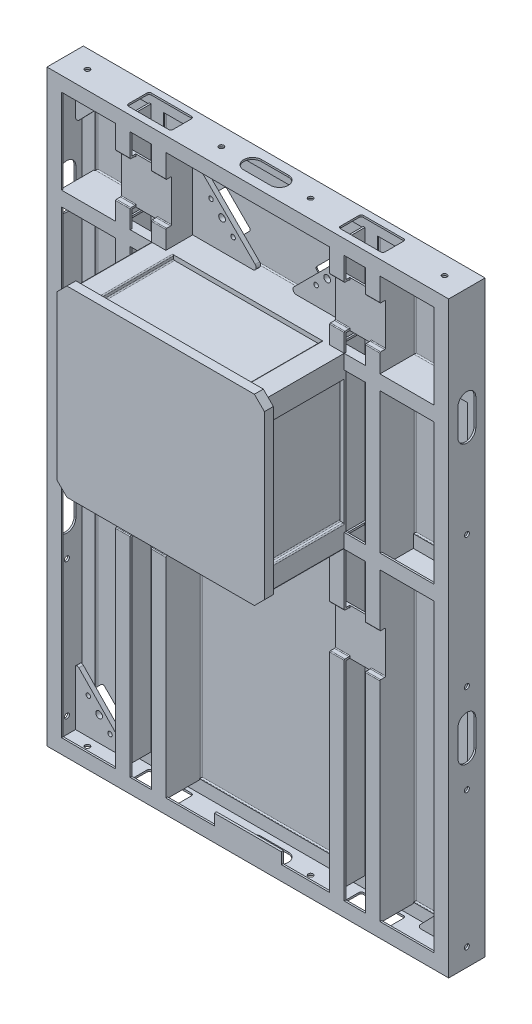
SolidWorks part; units mm, degrees
ref_plane "Alzado" through (0, 0, 0) normal (0, 0, 1) x (1, 0, 0)
ref_plane "Planta" through (0, 0, 0) normal (0, 1, 0) x (1, 0, 0)
ref_plane "Vista lateral" through (0, 0, 0) normal (1, 0, 0) x (0, 0, -1)
sketch "Croquis1" plane through (0, 0, 0) normal (0, 0, 1) x (1, 0, 0)
  line L1 (0, 0) -> (900, 0)
  line L2 (0, 0) -> (0, 2635)
  line L3 (0, 2635) -> (900, 2635)
  line L4 (900, 0) -> (900, 2635)
  dimension "D1" = 2635
  dimension "D2" = 900
extrude "Saliente-Extruir1" add sketch "Croquis1" along normal blind 5
sketch "Croquis3" plane through (0, 0, 5) normal (0, 0, 1) x (1, 0, 0)
  line L0 (900, 2635) -> (0, 2635) construction
  line L1 (0, 0) -> (65, 0)
  line L2 (0, 0) -> (0, 2125)
  line L3 (0, 2635) -> (65, 2635)
  line L4 (65, 65) -> (65, 1430)
  line L5 (900, 0) -> (900, 2635) construction
  line L6 (0, 2635) -> (900, 2635)
  line L7 (0, 2635) -> (0, 2570)
  line L8 (65, 2570) -> (308, 2570)
  line L9 (900, 2635) -> (900, 2570)
  line L10 (373, 2190) -> (468, 2190)
  line L11 (0, 0) -> (900, 0)
  line L12 (0, 0) -> (0, 65)
  line L13 (65, 65) -> (308, 65)
  line L14 (900, 0) -> (900, 65)
  line L15 (308, 0) -> (373, 0)
  line L16 (308, 65) -> (308, 1430)
  line L17 (308, 2635) -> (373, 2635)
  line L18 (373, 65) -> (373, 1430)
  line L19 (468, 0) -> (533, 0)
  line L20 (468, 65) -> (468, 1430)
  line L21 (468, 2635) -> (533, 2635)
  line L22 (533, 65) -> (533, 1430)
  line L23 (65, 1430) -> (308, 1430)
  line L24 (0, 1430) -> (0, 1495)
  line L25 (65, 1495) -> (308, 1495)
  line L26 (900, 1430) -> (900, 1495)
  line L27 (65, 2125) -> (308, 2125)
  line L28 (0, 2125) -> (0, 2190)
  line L29 (65, 2190) -> (308, 2190)
  line L30 (900, 2125) -> (900, 2190)
  line L31 (308, 2190) -> (308, 2570)
  line L32 (373, 2190) -> (373, 2570)
  line L33 (373, 2125) -> (468, 2125)
  line L34 (468, 2190) -> (468, 2570)
  line L35 (533, 2190) -> (900, 2190)
  line L36 (533, 2190) -> (533, 2570)
  line L37 (533, 2125) -> (900, 2125)
  line L38 (533, 2570) -> (900, 2570)
  line L39 (373, 2570) -> (468, 2570)
  line L40 (65, 2190) -> (65, 2570)
  line L41 (373, 1495) -> (468, 1495)
  line L42 (308, 1495) -> (308, 2125)
  line L43 (373, 1495) -> (373, 2125)
  line L44 (373, 1430) -> (468, 1430)
  line L45 (533, 1430) -> (900, 1430)
  line L46 (533, 1495) -> (900, 1495)
  line L47 (533, 1495) -> (533, 2125)
  line L48 (468, 1495) -> (468, 2125)
  line L49 (65, 1495) -> (65, 2125)
  line L50 (373, 65) -> (468, 65)
  line L51 (533, 65) -> (900, 65)
  line L52 (0, 2190) -> (0, 2635)
  line M11 (0, 2635) -> (0, 0)
  line M12 (0, 0) -> (900, 0)
  line M13 (900, 0) -> (900, 2635)
  line M14 (900, 2635) -> (0, 2635)
  dimension "D1" = 65
  dimension "D2" = 65
  dimension "D3" = 65
  dimension "D4" = 65
  dimension "D5" = 65
  dimension "D6" = 95
  dimension "D7" = 65
  dimension "D8" = 65
  dimension "D9" = 243
  dimension "D10" = 630
  dimension "D11" = 380
extrude "Saliente-Extruir2" add sketch "Croquis3" along normal blind 8 contours L51 L22 L45 L46 L47 L37 L35 L36 L38 L6 L2 L11 L50 L18 L44 L20 L48 L41 L43 L33 L4 L23 L16 L13 L32 L39 L34 M13 M14 M11 M12
sketch "Croquis4" plane through (0, 0, 13) normal (0, 0, 1) x (1, 0, 0)
  line L0 (308, 2627) -> (308, 2190)
  line L1 (533, 8) -> (533, 1430)
  line L2 (8, 2190) -> (308, 2190)
  line L3 (8, 2182) -> (308, 2182)
  line L4 (8, 1430) -> (308, 1430)
  line L5 (8, 1438) -> (308, 1438)
  line L6 (316, 2627) -> (316, 2190)
  line L7 (525, 8) -> (525, 1430)
  line L8 (8, 2182) -> (8, 1438)
  line L9 (316, 2190) -> (525, 2190)
  line L10 (316, 2182) -> (525, 2182)
  line L11 (8, 2190) -> (900, 2190) construction
  line L12 (308, 2182) -> (308, 1438)
  line L13 (8, 2182) -> (900, 2182) construction
  line L14 (316, 2182) -> (316, 1438)
  line L15 (308, 2627) -> (308, 8) construction
  line L16 (533, 2190) -> (900, 2190)
  line L17 (316, 2627) -> (316, 8) construction
  line L18 (525, 2190) -> (525, 2627)
  line L19 (533, 2190) -> (533, 2627)
  line L20 (525, 8) -> (525, 2627) construction
  line L21 (533, 2182) -> (900, 2182)
  line L22 (533, 8) -> (533, 2627) construction
  line L23 (308, 2627) -> (8, 2627)
  line L24 (525, 2627) -> (316, 2627)
  line L25 (316, 1438) -> (525, 1438)
  line L26 (900, 2627) -> (8, 2627)
  line L27 (8, 8) -> (900, 8)
  line L28 (8, 2627) -> (8, 8)
  line L29 (900, 2627) -> (533, 2627)
  line L30 (8, 8) -> (308, 8)
  line L31 (8, 2627) -> (8, 2190)
  line L32 (308, 1430) -> (308, 8)
  line L33 (8, 1438) -> (900, 1438) construction
  line L34 (316, 1430) -> (525, 1430)
  line L35 (316, 1430) -> (316, 8)
  line L36 (8, 1430) -> (900, 1430) construction
  line L37 (533, 1438) -> (900, 1438)
  line L38 (525, 1438) -> (525, 2182)
  line L39 (533, 1430) -> (900, 1430)
  line L40 (533, 1438) -> (533, 2182)
  line L41 (8, 1430) -> (8, 8)
  line L42 (316, 8) -> (525, 8)
  line L43 (533, 8) -> (900, 8)
  line L44 (8, 1430) -> (8, 1438)
  line L59 (8, 1430) -> (65, 1430)
  line L60 (8, 1430) -> (8, 1438)
  line L61 (8, 1438) -> (65, 1438)
  line L62 (65, 1430) -> (65, 1438)
  line L71 (900, 2635) -> (0, 2635)
  line L72 (900, 2635) -> (900, 0)
  line L73 (900, 0) -> (0, 0)
  line L74 (0, 2635) -> (0, 0)
  line M33 (533, 65) -> (533, 1430)
  line M34 (533, 1430) -> (900, 1430)
  line M35 (900, 1430) -> (900, 1495)
  line M37 (533, 1495) -> (533, 2125)
  line M39 (900, 2125) -> (900, 2190)
  line M40 (900, 2190) -> (533, 2190)
  line M41 (533, 2190) -> (533, 2570)
  line M43 (900, 2570) -> (900, 2635)
  line M44 (900, 2635) -> (0, 2635)
  line M45 (0, 2635) -> (0, 0)
  line M46 (0, 0) -> (900, 0)
  line M47 (900, 0) -> (900, 65)
  line M50 (373, 1430) -> (468, 1430)
  line M57 (65, 1430) -> (308, 1430)
  line M58 (308, 1430) -> (308, 65)
  line M63 (468, 2190) -> (373, 2190)
  line M64 (308, 2190) -> (65, 2190)
  line M67 (308, 2570) -> (308, 2190)
  dimension "D1" = 8
  dimension "D2" = 8
  dimension "D3" = 8
  dimension "D4" = 8
  dimension "D5" = 8
extrude "Saliente-Extruir4" add sketch "Croquis4" along normal blind 150 separate body contours L43 L1 L37 L40 L21 L19 L29 L42 L35 L34 L7 L41 L4 L32 L30 L38 L25 L14 L10 L31 L23 L0 L2 L24 L18 L9 M33 M34 M35 M37 M39 M40 M41 M43 M44 M45 M46 M47 M50 M57 M58 M67 M64 M63
sketch "Croquis6" plane through (0, 0, 163) normal (0, 0, 1) x (1, 0, 0)
  line L1 (65, 2570) -> (308, 2570)
  line L2 (65, 2570) -> (65, 2190)
  line L3 (65, 2190) -> (308, 2190)
  line L4 (308, 2570) -> (308, 2190)
  line L5 (373, 2570) -> (468, 2570)
  line L6 (373, 2570) -> (373, 2190)
  line L7 (373, 2190) -> (468, 2190)
  line L8 (468, 2570) -> (468, 2190)
  line L9 (65, 2125) -> (308, 2125)
  line L10 (65, 2125) -> (65, 1495)
  line L11 (65, 1495) -> (308, 1495)
  line L12 (308, 2125) -> (308, 1495)
  line L13 (373, 1495) -> (468, 1495)
  line L14 (373, 1495) -> (373, 2125)
  line L15 (373, 2125) -> (468, 2125)
  line L16 (900, 65) -> (533, 65)
  line L17 (533, 65) -> (533, 1430)
  line L18 (533, 1430) -> (900, 1430)
  line L31 (900, 0) -> (900, 65)
  line L32 (900, 65) -> (533, 65)
  line L33 (533, 65) -> (533, 1430)
  line L47 (900, 0) -> (900, 65)
  line L48 (468, 1495) -> (468, 2125)
  line L49 (65, 1430) -> (308, 1430)
  line L50 (65, 1430) -> (65, 65)
  line L51 (65, 65) -> (308, 65)
  line L52 (308, 1430) -> (308, 65)
  line L53 (373, 65) -> (468, 65)
  line L54 (373, 65) -> (373, 1430)
  line L55 (373, 1430) -> (468, 1430)
  line L56 (468, 65) -> (468, 1430)
  line L64 (533, 1430) -> (900, 1430)
  line L66 (900, 1430) -> (900, 1495)
  line L68 (900, 1430) -> (900, 1495)
  line L70 (900, 1495) -> (533, 1495)
  line L72 (900, 1495) -> (533, 1495)
  line L74 (533, 1495) -> (533, 2125)
  line L76 (533, 1495) -> (533, 2125)
  line L78 (533, 2125) -> (900, 2125)
  line L80 (533, 2125) -> (900, 2125)
  line L82 (900, 2125) -> (900, 2190)
  line L84 (900, 2125) -> (900, 2190)
  line L86 (900, 2190) -> (533, 2190)
  line L87 (900, 2190) -> (533, 2190)
  line L88 (533, 2190) -> (533, 2570)
  line L89 (533, 2190) -> (533, 2570)
  line L90 (533, 2570) -> (900, 2570)
  line L91 (533, 2570) -> (900, 2570)
  line L92 (900, 2570) -> (900, 2635)
  line L93 (900, 2570) -> (900, 2635)
  line L94 (900, 2635) -> (0, 2635)
  line L95 (900, 2635) -> (0, 2635)
  line L96 (0, 2635) -> (0, 0)
  line L97 (0, 2635) -> (0, 0)
  line L98 (0, 0) -> (900, 0)
  line L99 (0, 0) -> (900, 0)
  dimension "D1" = 0
extrude "Saliente-Extruir5" add sketch "Croquis6" against normal blind 8
sketch "Croquis7" plane through (0, 0, 0) normal (-1, 0, 0) x (0, 0, 1)
  line L0 (0, 2135) -> (163, 2135) construction
  line L1 (0, 2635) -> (0, 0) construction
  line L2 (163, 2635) -> (163, 0) construction
  line L3 (81.5, 2635) -> (81.5, 0) construction
  line L4 (163, 2635) -> (13, 2635) construction
  line L5 (163, 0) -> (13, 0) construction
  line L6 (81.5, 2195) -> (81.5, 2075) construction
  line L7 (121.5, 2195) -> (121.5, 2075)
  line L8 (41.5, 2195) -> (41.5, 2075)
  line L9 (81.5, 950) -> (81.5, 830) construction
  line L10 (121.5, 950) -> (121.5, 830)
  line L11 (41.5, 950) -> (41.5, 830)
  arc A0 (121.5, 2195) -> (41.5, 2195) centre (81.5, 2195) ccw
  arc A1 (41.5, 2075) -> (121.5, 2075) centre (81.5, 2075) ccw
  circle A2 centre (81.5, 1680) radius 11
  circle A3 centre (81.5, 1090) radius 11
  circle A4 centre (81.5, 80) radius 11
  circle A5 centre (81.5, 690) radius 11
  arc A6 (121.5, 950) -> (41.5, 950) centre (81.5, 950) ccw
  arc A7 (41.5, 830) -> (121.5, 830) centre (81.5, 830) ccw
  point P6 (81.5, 2135)
  point P15 (81.5, 2135)
  point P30 (81.5, 890)
  dimension "D3" = 40
  dimension "D4" = 22
  dimension "D8" = 200
  dimension "D1" = 500
  dimension "D2" = 60
  dimension "D5" = 955
  dimension "D6" = 80
  dimension "D7" = 890
  dimension "D9" = 200
extrude "Cortar-Extruir1" cut sketch "Croquis7" against normal blind 50
sketch "Croquis9" plane through (0, 0, 13) normal (0, 0, 1) x (1, 0, 0)
  line L0 (533, 8) -> (900, 8) construction
  line L1 (533, 8) -> (533, 1430) construction
  line L2 (533, 1430) -> (900, 1430) construction
  line L3 (533, 1438) -> (900, 1438) construction
  line L4 (533, 1438) -> (533, 2182) construction
  line L5 (533, 2182) -> (900, 2182) construction
  line L6 (533, 2190) -> (900, 2190) construction
  line L7 (533, 2190) -> (533, 2627) construction
  line L8 (900, 2627) -> (533, 2627) construction
  line L9 (8, 1430) -> (8, 1438) construction
  line L10 (8, 1430) -> (8, 1438) construction
  line L11 (65, 2570) -> (900, 2570)
  line L12 (316, 65) -> (525, 65)
  line L13 (65, 65) -> (900, 65)
  line L14 (8, 2182) -> (8, 1438) construction
  line L15 (8, 2182) -> (308, 2182) construction
  line L16 (308, 2182) -> (308, 1438) construction
  line L17 (8, 1438) -> (308, 1438) construction
  line L18 (8, 1430) -> (308, 1430) construction
  line L19 (308, 1430) -> (308, 8) construction
  line L20 (8, 8) -> (308, 8) construction
  line L21 (8, 1430) -> (8, 8) construction
  line L22 (316, 2627) -> (316, 2190) construction
  line L23 (316, 2190) -> (525, 2190) construction
  line L24 (525, 2190) -> (525, 2627) construction
  line L25 (525, 2627) -> (316, 2627) construction
  line L26 (308, 2627) -> (308, 2190) construction
  line L27 (308, 2627) -> (8, 2627) construction
  line L28 (8, 2627) -> (8, 2190) construction
  line L29 (8, 2190) -> (308, 2190) construction
  line L30 (525, 1438) -> (525, 2182) construction
  line L31 (316, 2182) -> (525, 2182) construction
  line L32 (316, 2182) -> (316, 1438) construction
  line L33 (316, 1438) -> (525, 1438) construction
  line L34 (525, 8) -> (525, 1430) construction
  line L35 (316, 8) -> (525, 8) construction
  line L36 (316, 1430) -> (316, 8) construction
  line L37 (316, 1430) -> (525, 1430) construction
  line L38 (900, 2635) -> (0, 2635) construction
  line L39 (0, 2635) -> (0, 0) construction
  line L40 (900, 0) -> (0, 0) construction
  line L41 (900, 2635) -> (900, 0) construction
  line L42 (533, 8) -> (900, 8)
  line L43 (533, 65) -> (533, 1430)
  line L44 (533, 1430) -> (900, 1430)
  line L45 (533, 1438) -> (900, 1438)
  line L46 (533, 1438) -> (533, 2182)
  line L47 (533, 2182) -> (900, 2182)
  line L48 (533, 2190) -> (900, 2190)
  line L49 (533, 2190) -> (533, 2570)
  line L50 (900, 2627) -> (533, 2627)
  line L51 (8, 1430) -> (8, 1438)
  line L52 (8, 1430) -> (8, 1438)
  line L53 (65, 65) -> (65, 2570)
  line L54 (533, 65) -> (900, 65)
  line L55 (60, 60) -> (900, 60)
  line L56 (8, 2182) -> (8, 1438)
  line L57 (65, 2182) -> (308, 2182)
  line L58 (308, 2182) -> (308, 1438)
  line L59 (65, 1438) -> (308, 1438)
  line L60 (65, 1430) -> (308, 1430)
  line L61 (308, 1430) -> (308, 65)
  line L62 (8, 8) -> (308, 8)
  line L63 (8, 1430) -> (8, 8)
  line L64 (316, 2570) -> (316, 2190)
  line L65 (316, 2190) -> (525, 2190)
  line L66 (525, 2190) -> (525, 2570)
  line L67 (525, 2627) -> (316, 2627)
  line L68 (308, 2570) -> (308, 2190)
  line L69 (308, 2627) -> (8, 2627)
  line L70 (8, 2627) -> (8, 2190)
  line L71 (65, 2190) -> (308, 2190)
  line L72 (525, 1438) -> (525, 2182)
  line L73 (316, 2182) -> (525, 2182)
  line L74 (316, 2182) -> (316, 1438)
  line L75 (316, 1438) -> (525, 1438)
  line L76 (525, 65) -> (525, 1430)
  line L77 (316, 8) -> (525, 8)
  line L78 (316, 1430) -> (316, 65)
  line L79 (316, 1430) -> (525, 1430)
  line L80 (900, 2635) -> (0, 2635)
  line L81 (0, 2635) -> (0, 0)
  line L82 (900, 0) -> (0, 0)
  line L83 (900, 2635) -> (900, 0)
  line L84 (8, 2627) -> (65, 2627)
  line L85 (8, 2627) -> (8, 8)
  line L86 (8, 8) -> (65, 8)
  line L87 (65, 2570) -> (65, 65)
  line L88 (8, 8) -> (900, 8)
  line L89 (8, 8) -> (8, 65)
  line L90 (65, 65) -> (308, 65)
  line L91 (900, 8) -> (900, 65)
  line L92 (8, 2627) -> (900, 2627)
  line L93 (8, 2627) -> (8, 2570)
  line L94 (65, 2570) -> (900, 2570)
  line L95 (900, 2627) -> (900, 2570)
  line L96 (65, 65) -> (65, 1430) construction
  line L97 (60, 60) -> (60, 2575)
  line L98 (60, 2575) -> (900, 2575)
  line M40 (900, 0) -> (900, 65)
  dimension "D1" = 5
extrude "Cortar-Extruir3" cut sketch "Croquis9" along normal blind 142 contours L97 L98 L95 L50 L92 L67 L69 L70 L85 L56 L51 L63 L62 L88 L77 L42 L55 M40
fillet "Redondeo1" radius 5 30 edges at (716.5, 1430, 5) (716.5, 65, 5) (533, 747.5, 5) (186.5, 1430, 5) (308, 747.5, 5) (186.5, 65, 5) (65, 747.5, 5) (186.5, 2125, 5) (308, 1810, 5) (186.5, 1495, 5) (65, 1810, 5) (716.5, 2570, 5) (716.5, 2190, 5) (533, 2380, 5) (186.5, 2570, 5) (308, 2380, 5) (186.5, 2190, 5) (65, 2380, 5) (420.5, 2570, 5) (468, 2380, 5) (420.5, 2190, 5) (373, 2380, 5) (373, 1810, 5) (420.5, 2125, 5) (468, 1810, 5) (420.5, 1495, 5) (420.5, 1430, 5) (468, 747.5, 5) (420.5, 65, 5) (373, 747.5, 5)
sketch "Croquis13" plane through (0, 0, 5) normal (0, 0, 1) x (1, 0, 0)
  line L0 (533, 1438) -> (900, 1438) construction
  line L1 (533, 2182) -> (900, 2182) construction
  line L2 (533, 1438) -> (900, 1438)
  line L3 (533, 2182) -> (900, 2182)
  line L4 (533, 2125) -> (533, 1495)
  line L5 (533, 1495) -> (900, 1495)
  line L6 (900, 1495) -> (900, 2125)
  line L7 (900, 2125) -> (533, 2125)
  line L8 (533, 2125) -> (533, 1495)
  line L9 (533, 1495) -> (900, 1495)
  line L10 (900, 1495) -> (900, 2125)
  line L11 (900, 2125) -> (533, 2125)
  line L12 (900, 1438) -> (900, 1495)
  line L13 (533, 1438) -> (533, 1495)
  line L14 (533, 2125) -> (533, 2182)
  line L15 (900, 2125) -> (900, 2182)
  line M5 (533, 2125) -> (533, 1495)
  line M6 (533, 1495) -> (900, 1495)
  line M7 (900, 1495) -> (900, 2125)
  line M8 (900, 2125) -> (533, 2125)
  dimension "D1" = 0
extrude "Saliente-Extruir10" add sketch "Croquis13" along normal blind 158 contours L15 L3 L14 M8 | M8 M5 M6 M7 | L13 L2 L12 M6
sketch "Croquis14" plane through (0, 0, 163) normal (0, 0, 1) x (1, 0, 0)
  line L1 (308, 2570) -> (533, 2570)
  line L2 (308, 2570) -> (308, 2190)
  line L3 (308, 2190) -> (533, 2190)
  line L4 (533, 2570) -> (533, 2190)
  line L5 (308, 1430) -> (533, 1430)
  line L6 (308, 1430) -> (308, 65)
  line L7 (308, 65) -> (533, 65)
  line L8 (533, 1430) -> (533, 65)
  line L9 (308, 1200) -> (533, 1200)
  line L10 (308, 1200) -> (308, 994)
  line L11 (308, 994) -> (533, 994)
  line L12 (533, 1200) -> (533, 994)
  line L13 (308, 2472) -> (533, 2472)
  line L14 (308, 2472) -> (308, 2266)
  line L15 (308, 2266) -> (533, 2266)
  line L16 (533, 2472) -> (533, 2266)
  dimension "D1" = 98
  dimension "D2" = 206
  dimension "D3" = 206
  dimension "D4" = 230
extrude "Saliente-Extruir11" add sketch "Croquis14" against normal blind 33 contours L15 L16 L13 L14 | L11 L12 L9 L10
sketch "Croquis15" plane through (0, 0, 163) normal (0, 0, 1) x (1, 0, 0)
  line L0 (533, 2464) -> (468, 2464)
  line L1 (308, 2274) -> (373, 2274)
  line L2 (533, 1192) -> (468, 1192)
  line L3 (308, 1002) -> (373, 1002)
  line L4 (533, 1200) -> (308, 1200)
  line L5 (533, 994) -> (533, 1200)
  line L6 (308, 994) -> (533, 994)
  line L7 (308, 1200) -> (308, 994)
  line L8 (533, 1200) -> (308, 1200)
  line L9 (533, 994) -> (533, 1200)
  line L10 (308, 994) -> (533, 994)
  line L11 (308, 1200) -> (308, 994)
  line L12 (533, 1430) -> (308, 1430)
  line L13 (533, 65) -> (533, 1430)
  line L14 (308, 65) -> (533, 65)
  line L15 (308, 1430) -> (308, 65)
  line L16 (533, 1430) -> (308, 1430)
  line L17 (533, 65) -> (533, 1430)
  line L18 (308, 65) -> (533, 65)
  line L19 (308, 1430) -> (308, 65)
  line L20 (533, 2570) -> (308, 2570)
  line L21 (533, 2190) -> (533, 2570)
  line L22 (308, 2190) -> (533, 2190)
  line L23 (308, 2570) -> (308, 2190)
  line L24 (533, 2570) -> (308, 2570)
  line L25 (533, 2190) -> (533, 2570)
  line L26 (308, 2190) -> (533, 2190)
  line L27 (308, 2570) -> (308, 2190)
  line L28 (533, 2472) -> (308, 2472)
  line L29 (533, 2266) -> (533, 2472)
  line L30 (308, 2266) -> (533, 2266)
  line L31 (308, 2472) -> (308, 2266)
  line L32 (533, 2472) -> (308, 2472)
  line L33 (533, 2266) -> (533, 2472)
  line L34 (308, 2266) -> (533, 2266)
  line L35 (308, 2472) -> (308, 2266)
  line L36 (373, 994) -> (373, 1002)
  line L37 (373, 65) -> (373, 1430) construction
  line L38 (468, 994) -> (468, 1002)
  line L39 (373, 1200) -> (373, 1192)
  line L40 (468, 1200) -> (468, 1192)
  line L41 (373, 2472) -> (373, 2464)
  line L42 (468, 2472) -> (468, 2464)
  line L43 (373, 2274) -> (373, 2266)
  line L44 (468, 2274) -> (533, 2274)
  line L45 (468, 2274) -> (468, 2266)
  line L46 (308, 2274) -> (533, 2274) construction
  line L47 (373, 2464) -> (308, 2464)
  line L48 (373, 1192) -> (308, 1192)
  line L49 (533, 2464) -> (308, 2464) construction
  line L50 (468, 1002) -> (533, 1002)
  line L51 (533, 1192) -> (308, 1192) construction
  line L53 (308, 1002) -> (533, 1002) construction
  line M25 (533, 65) -> (533, 1430)
  line M29 (533, 2190) -> (533, 2570)
  line M37 (308, 1430) -> (308, 65)
  line M49 (308, 2570) -> (308, 2190)
  dimension "D1" = 0
  dimension "D2" = 0
  dimension "D3" = 0
  dimension "D4" = 0
  dimension "D5" = 8
extrude "Cortar-Extruir4" cut sketch "Croquis15" against normal blind 25 contours L3 L2 M37 M25 | L1 L0 M49 M29
fillet "Redondeo2" radius 3.5 16 edges at (500.5, 2274, 138) (340.5, 2274, 138) (500.5, 2464, 138) (340.5, 2464, 138) (500.5, 1192, 138) (340.5, 1192, 138) (500.5, 1002, 138) (340.5, 1002, 138) (500.5, 1002, 163) (340.5, 1002, 163) (500.5, 1192, 163) (340.5, 1192, 163) (500.5, 2274, 163) (340.5, 2274, 163) (500.5, 2464, 163) (340.5, 2464, 163)
ref_plane "Plano1" through (0, 0, 43) normal (0, 0, 1) x (1, 0, 0)
sketch "Croquis16" plane through (0, 0, 43) normal (0, 0, -1) x (-1, 0, 0)
  line L0 (-23, 255.2654) -> (-248, 23)
  line L1 (-8, 8) -> (-900, 8) construction
  line L2 (-8, 2627) -> (-8, 8) construction
  line L5 (0, 0) -> (0, 2635)
  line L6 (0, 2635) -> (-900, 2635)
  line L7 (-900, 2635) -> (-900, 0)
  line L8 (-900, 0) -> (0, 0)
  line L9 (0, 0) -> (0, 2635)
  line L10 (0, 2635) -> (-900, 2635)
  line L11 (-900, 2635) -> (-900, 0)
  line L12 (-900, 0) -> (0, 0)
  line L13 (-8, 8) -> (-8, 2627) construction
  line L14 (-248, 8) -> (-8, 8)
  line L15 (-8, 8) -> (-8, 255.2654)
  line L16 (-8, 1317.5) -> (-65, 1317.5)
  line L17 (-65, 65) -> (-65, 1430) construction
  line L18 (-248, 2627) -> (-8, 2627)
  line L20 (-8, 2627) -> (-8, 2379.7346)
  line L21 (-65.2476, 168.5368) -> (-162.6573, 67.9816) construction
  line L22 (-135.5, 139.1327) -> (-113.9525, 118.2592)
  line L23 (-248, 2627) -> (-8, 2627)
  line L24 (-23, 2379.7346) -> (-248, 2612)
  line L25 (-8, 2627) -> (-8, 2379.7346)
  arc A0 (-248, 23) -> (-248, 8) centre (-240.2578, 15.5) ccw
  arc A1 (-23, 255.2654) -> (-8, 255.2654) centre (-15.5, 248) cw
  arc A2 (-248, 2612) -> (-248, 2627) centre (-240.2578, 2619.5) cw
  arc A3 (-23, 2379.7346) -> (-8, 2379.7346) centre (-15.5, 2387) ccw
  circle A4 centre (-113.9525, 118.2592) radius 15
  circle A5 centre (-65.2476, 168.5368) radius 10
  circle A6 centre (-162.6573, 67.9816) radius 10
  circle A7 centre (-162.6573, 2567.0184) radius 10
  circle A8 centre (-113.9525, 2516.7408) radius 15
  circle A9 centre (-65.2476, 2466.4632) radius 10
  arc A10 (-248, 2612) -> (-248, 2627) centre (-240.2578, 2619.5) cw
  arc A11 (-23, 2379.7346) -> (-8, 2379.7346) centre (-15.5, 2387) ccw
  dimension "D4" = 20
  dimension "D5" = 240
  dimension "D9" = 30
  dimension "D2" = 15
  dimension "D3" = 240
  dimension "D6" = 15
  dimension "D7" = 70
  dimension "D8" = 30
  dimension "D1" = 0
extrude "Saliente-Extruir12" add sketch "Croquis16" along normal blind 20
sketch "Croquis17" plane through (0, 0, 43) normal (0, 0, 1) x (1, 0, 0)
  line L0 (316, 2575) -> (316, 2190)
  line L1 (316, 2190) -> (525, 2190)
  line L2 (316, 1430) -> (525, 1430)
  line L3 (316, 1430) -> (316, 60)
  line L4 (316, 1438) -> (316, 2182)
  line L5 (316, 2182) -> (316, 1438) construction
  line L6 (316, 2182) -> (525, 2182) construction
  line L7 (316, 1810) -> (525, 1810) construction
  line L8 (525, 1438) -> (525, 2182) construction
  line L9 (900, 1430) -> (533, 1430) construction
  line L10 (533, 1430) -> (533, 60) construction
  line L11 (900, 2190) -> (533, 2190)
  line L12 (533, 2190) -> (533, 2575)
  line L13 (558.6066, 1150) -> (813, 1404.3934)
  line L15 (533, 65) -> (533, 1430) construction
  line L16 (533, 1160.6066) -> (533, 1430)
  line L17 (802.3934, 1430) -> (533, 1430)
  line L18 (615.0926, 1248.9124) -> (714.0876, 1347.9074) construction
  line L19 (685.8033, 1277.1967) -> (664.5901, 1298.4099)
  line L20 (802.3934, 2190) -> (533, 2190)
  line L21 (558.6066, 2470) -> (813, 2215.6066)
  line L22 (533, 2459.3934) -> (533, 2190)
  arc A0 (813, 1404.3934) -> (802.3934, 1430) centre (802.3934, 1415) ccw
  arc A1 (558.6066, 1150) -> (533, 1160.6066) centre (548, 1160.6066) cw
  circle A2 centre (664.5901, 1298.4099) radius 15
  circle A3 centre (714.0876, 1347.9074) radius 10
  circle A4 centre (615.0926, 1248.9124) radius 10
  circle A5 centre (615.0926, 2371.0876) radius 10
  circle A6 centre (714.0876, 2272.0926) radius 10
  circle A7 centre (664.5901, 2321.5901) radius 15
  arc A8 (813, 2215.6066) -> (802.3934, 2190) centre (802.3934, 2205) cw
  arc A9 (558.6066, 2470) -> (533, 2459.3934) centre (548, 2459.3934) ccw
  dimension "D5" = 20
  dimension "D6" = 30
  dimension "D1" = 280
  dimension "D2" = 280
  dimension "D3" = 15
  dimension "D4" = 30
  dimension "D7" = 70
extrude "Saliente-Extruir13" add sketch "Croquis17" against normal blind 20
sketch "Croquis18" plane through (0, 0, 0) normal (0, -1, 0) x (1, 0, 0)
  line L0 (0, 0) -> (0, 163)
  line L1 (0, 81.5) -> (900, 81.5) construction
  line L2 (900, 163) -> (900, 0) construction
  line L3 (0, 163) -> (900, 163) construction
  line L4 (335, 30) -> (515, 30)
  line L5 (325, 40) -> (325, 123)
  line L6 (335, 133) -> (515, 133)
  line L7 (525, 40) -> (525, 123)
  line L9 (960, 81.5) -> (840, 81.5) construction
  line L10 (960, 41.5) -> (840, 41.5)
  line L11 (960, 121.5) -> (840, 121.5)
  circle A0 centre (100, 81.5) radius 11
  circle A1 centre (700, 81.5) radius 11
  arc A2 (960, 41.5) -> (960, 121.5) centre (960, 81.5) ccw
  arc A3 (840, 121.5) -> (840, 41.5) centre (840, 81.5) ccw
  arc A4 (335, 30) -> (325, 40) centre (335, 40) cw
  arc A5 (515, 30) -> (525, 40) centre (515, 40) ccw
  arc A6 (515, 133) -> (525, 123) centre (515, 123) cw
  arc A7 (335, 133) -> (325, 123) centre (335, 123) ccw
  point P16 (325, 81.5)
  point P21 (900, 81.5)
  point P33 (525, 133)
  point P36 (325, 133)
  line M18 (900, 0) -> (900, 163)
  dimension "D6" = 60
  dimension "D5" = 40
  dimension "D7" = 200
  dimension "D9" = 22
  dimension "D10" = 10
  dimension "D1" = 200
  dimension "D2" = 30
  dimension "D3" = 325
  dimension "D4" = 41.5
  dimension "D8" = 100
extrude "Cortar-Extruir5" cut sketch "Croquis18" against normal blind 30 contours A0 | L6 A7 L5 A4 L4 A5 L7 A6 | L11 A3 L10 M18 | A1
sketch "Croquis19" plane through (0, 0, 163) normal (0, 0, 1) x (1, 0, 0)
  line L1 (900, 65) -> (750, 65)
  line L2 (900, 65) -> (900, 115)
  line L3 (900, 115) -> (750, 115)
  line L4 (750, 65) -> (750, 115)
  dimension "D1" = 150
  dimension "D2" = 50
extrude "Saliente-Extruir14" add sketch "Croquis19" against normal blind 10
ref_plane "Plano2" through (0, 1080, 0) normal (0, 1, 0) x (1, 0, 0)
sketch "Croquis21" plane through (0, 1080, 0) normal (0, 1, 0) x (1, 0, 0)
  line L0 (316, -13) -> (316, -155) construction
  line L1 (326, -13) -> (515, -13)
  line L2 (316, -23) -> (316, -120)
  line L3 (326, -130) -> (515, -130)
  line L4 (525, -23) -> (525, -120)
  line L5 (8, -13) -> (900, -13) construction
  line L6 (311, -23) -> (311, -120)
  line L7 (326, -135) -> (515, -135)
  line L8 (530, -23) -> (530, -120)
  line L9 (326, -8) -> (515, -8)
  line L10 (323.5, -23) -> (323.5, -120)
  line L11 (326, -122.5) -> (515, -122.5)
  line L12 (517.5, -23) -> (517.5, -120)
  line L13 (326, -20.5) -> (515, -20.5)
  arc A0 (316, -120) -> (326, -130) centre (326, -120) ccw
  arc A1 (515, -130) -> (525, -120) centre (515, -120) ccw
  arc A2 (525, -23) -> (515, -13) centre (515, -23) ccw
  arc A3 (326, -13) -> (316, -23) centre (326, -23) ccw
  arc A4 (311, -120) -> (326, -135) centre (326, -120) ccw
  arc A5 (515, -135) -> (530, -120) centre (515, -120) ccw
  arc A6 (530, -23) -> (515, -8) centre (515, -23) ccw
  arc A7 (326, -8) -> (311, -23) centre (326, -23) ccw
  arc A8 (323.5, -120) -> (326, -122.5) centre (326, -120) ccw
  arc A9 (515, -122.5) -> (517.5, -120) centre (515, -120) ccw
  arc A10 (517.5, -23) -> (515, -20.5) centre (515, -23) ccw
  arc A11 (326, -20.5) -> (323.5, -23) centre (326, -23) ccw
  point P14 (525, -130)
  point P19 (316, -13)
  dimension "D1" = 10
  dimension "D2" = 5
  dimension "D3" = 7.5
extrude "Cortar-Extruir6" cut sketch "Croquis21" along normal blind 1450 contours L10 A8 L11 A9 L12 A10 L13 A11
sketch "Croquis22" plane through (0, 2635, 0) normal (0, 1, 0) x (1, 0, 0)
  line L0 (0, 0) -> (0, -163) construction
  line L1 (0, 0) -> (0, -163)
  line L2 (960, -41.5) -> (840, -41.5)
  line L3 (840, -121.5) -> (960, -121.5)
  line L4 (960, -41.5) -> (840, -41.5)
  line L5 (840, -121.5) -> (960, -121.5)
  line L8 (325, -40) -> (325, -123)
  line L9 (515, -30) -> (335, -30)
  line L10 (525, -123) -> (525, -40)
  line L11 (335, -133) -> (515, -133)
  line L12 (325, -40) -> (325, -123)
  line L13 (515, -30) -> (335, -30)
  line L14 (525, -123) -> (525, -40)
  line L15 (335, -133) -> (515, -133)
  circle A1 centre (700, -81.5) radius 11
  circle A2 centre (700, -81.5) radius 11
  circle A3 centre (100, -81.5) radius 11
  circle A4 centre (100, -81.5) radius 11
  arc A6 (840, -41.5) -> (840, -121.5) centre (840, -81.5) ccw
  arc A7 (960, -121.5) -> (960, -41.5) centre (960, -81.5) ccw
  arc A8 (840, -41.5) -> (840, -121.5) centre (840, -81.5) ccw
  arc A9 (960, -121.5) -> (960, -41.5) centre (960, -81.5) ccw
  arc A12 (335, -30) -> (325, -40) centre (335, -40) ccw
  arc A13 (525, -40) -> (515, -30) centre (515, -40) ccw
  arc A14 (515, -133) -> (525, -123) centre (515, -123) ccw
  arc A15 (325, -123) -> (335, -133) centre (335, -123) ccw
  arc A16 (335, -30) -> (325, -40) centre (335, -40) ccw
  arc A17 (525, -40) -> (515, -30) centre (515, -40) ccw
  arc A18 (515, -133) -> (525, -123) centre (515, -123) ccw
  arc A19 (325, -123) -> (335, -133) centre (335, -123) ccw
  line M18 (900, -163) -> (900, 0)
  dimension "D1" = 0
  dimension "D2" = 0
  dimension "D3" = 0
  dimension "D4" = 0
extrude "Cortar-Extruir7" cut sketch "Croquis22" against normal blind 50 contours A4 | L12 A19 L15 A18 L14 A17 L13 A16 | L4 A8 L5 M18 | A2
sketch "Croquis23" plane through (0, 0, 0) normal (0, 0, -1) x (-1, 0, 0)
  line L35 (0, 0) -> (0, 2635) construction
  line L36 (0, 2635) -> (-900, 2635) construction
  line L37 (-900, 2635) -> (-900, 0) construction
  line L38 (-900, 0) -> (0, 0) construction
  line L49 (0, 0) -> (0, 2635)
  line L50 (0, 2635) -> (-900, 2635)
  line L51 (-900, 2635) -> (-900, 2190)
  line L52 (-900, 0) -> (0, 0)
  line L57 (-678.7322, 2236.7373) -> (-579.7373, 2335.7322)
  line L59 (-579.7373, 2349.8744) -> (-636.3058, 2406.4429)
  line L61 (-692.8744, 2236.7373) -> (-749.4429, 2293.3058)
  line L63 (-749.4429, 2307.448) -> (-650.448, 2406.4429)
  line L65 (-29.5597, 2487.1121) -> (-87.0198, 2431.4494)
  line L66 (-29.335, 2501.2524) -> (-126.7448, 2601.8076)
  line L67 (-101.1602, 2431.674) -> (-198.5699, 2532.2292)
  line L68 (-140.8851, 2602.0323) -> (-198.3452, 2546.3696)
  line L74 (-128.0946, 33.4064) -> (-29.0997, 132.4013)
  line L75 (-142.2367, 33.4064) -> (-198.8053, 89.9749)
  line L76 (-29.0997, 146.5435) -> (-85.6682, 203.112)
  line L77 (-198.8053, 104.117) -> (-99.8103, 203.112)
  line L78 (-579.7373, 1270.1256) -> (-636.3058, 1213.5571)
  line L79 (-650.448, 1213.5571) -> (-749.4429, 1312.552)
  line L80 (-692.8744, 1383.2627) -> (-749.4429, 1326.6942)
  line L81 (-579.7373, 1284.2678) -> (-678.7322, 1383.2627)
  arc A20 (-248, 2627) -> (-248, 2612) centre (-240.2578, 2619.5) ccw construction
  arc A21 (-248, 2627) -> (-248, 2612) centre (-240.2578, 2619.5) ccw construction
  arc A22 (-23, 2379.7346) -> (-8, 2379.7346) centre (-15.5, 2387) ccw construction
  arc A23 (-23, 2379.7346) -> (-8, 2379.7346) centre (-15.5, 2387) ccw construction
  arc A32 (-248, 2627) -> (-248, 2612) centre (-240.2578, 2619.5) ccw
  arc A33 (-248, 2627) -> (-248, 2612) centre (-240.2578, 2619.5) ccw
  arc A34 (-23, 2379.7346) -> (-8, 2379.7346) centre (-15.5, 2387) ccw
  arc A35 (-23, 2379.7346) -> (-8, 2379.7346) centre (-15.5, 2387) ccw
  arc A44 (-692.8744, 2236.7373) -> (-678.7322, 2236.7373) centre (-685.8033, 2243.8084) ccw
  arc A45 (-579.7373, 2335.7322) -> (-579.7373, 2349.8744) centre (-586.8084, 2342.8033) ccw
  arc A46 (-636.3058, 2406.4429) -> (-650.448, 2406.4429) centre (-643.3769, 2399.3718) ccw
  arc A47 (-749.4429, 2307.448) -> (-749.4429, 2293.3058) centre (-742.3718, 2300.3769) ccw
  arc A52 (-29.5597, 2487.1121) -> (-29.335, 2501.2524) centre (-36.5175, 2494.2946) ccw
  arc A53 (-126.7448, 2601.8076) -> (-140.8851, 2602.0323) centre (-133.9273, 2594.8498) ccw
  arc A54 (-198.3452, 2546.3696) -> (-198.5699, 2532.2292) centre (-191.3874, 2539.187) ccw
  arc A55 (-101.1602, 2431.674) -> (-87.0198, 2431.4494) centre (-93.9776, 2438.6319) ccw
  arc A57 (-29.0997, 132.4013) -> (-29.0997, 146.5435) centre (-36.1707, 139.4724) ccw
  arc A58 (-198.8053, 104.117) -> (-198.8053, 89.9749) centre (-191.7342, 97.046) ccw
  arc A59 (-142.2367, 33.4064) -> (-128.0946, 33.4064) centre (-135.1657, 40.4774) ccw
  arc A60 (-85.6682, 203.112) -> (-99.8103, 203.112) centre (-92.7393, 196.0409) ccw
  arc A61 (-650.448, 1213.5571) -> (-636.3058, 1213.5571) centre (-643.3769, 1220.6282) ccw
  arc A62 (-678.7322, 1383.2627) -> (-692.8744, 1383.2627) centre (-685.8033, 1376.1916) ccw
  arc A63 (-579.7373, 1270.1256) -> (-579.7373, 1284.2678) centre (-586.8084, 1277.1967) ccw
  arc A65 (-749.4429, 1326.6942) -> (-749.4429, 1312.552) centre (-742.3718, 1319.6231) ccw
  point P90 (-685.8033, 2229.6662)
  point P105 (-643.3769, 2413.514)
  point P108 (-756.514, 2300.3769)
  dimension "D3" = 10
  dimension "D9" = 10
  dimension "D1" = 100
  dimension "D2" = 160
  dimension "D6" = 100
  dimension "D7" = 160
extrude "Cortar-Extruir10" cut sketch "Croquis23" against normal blind 15 and the other way through all contours L63 A47 L61 A44 L57 A45 L59 A46 | L67 A55 L65 A52 L66 A53 L68 A54 | L80 A65 L79 A61 L78 A63 L81 A62 | L76 A60 L77 A58 L75 A59 L74 A57
mirror "Simetría4" about plane through (900, 0, 5) normal (-1, 0, 0) of bodies 126
sketch "Croquis24" plane through (0, 0, 163) normal (0, 0, 1) x (1, 0, 0)
  line L1 (472, 1430) -> (562, 1430)
  line L2 (467, 2095) -> (467, 2185)
  line L3 (1237, 2190) -> (1332, 2190)
  line L4 (1332, 1435) -> (1332, 1525)
  line L5 (1332, 1495) -> (1332, 2125) construction
  line L13 (572, 1450) -> (1227, 1450)
  line L14 (567, 1445) -> (567, 1435)
  line L15 (572, 2170) -> (1227, 2170)
  line L16 (472, 2190) -> (562, 2190)
  line L17 (567, 2185) -> (567, 2175)
  line L18 (802.3934, 2190) -> (533, 2190) construction
  line L19 (1232, 2175) -> (1232, 2185)
  line L20 (472, 2090) -> (482, 2090)
  line L21 (1232, 1445) -> (1232, 1435)
  line L22 (487, 2085) -> (487, 1535)
  line L23 (467, 1525) -> (467, 1435)
  line L24 (1237, 1430) -> (1327, 1430)
  line L25 (487, 1810) -> (1313, 1810) construction
  line L26 (900, 1810) -> (900, 1425) construction
  line L27 (1262, 1425) -> (538, 1425) construction
  line L28 (482, 1530) -> (472, 1530)
  line L29 (1327, 1530) -> (1317, 1530)
  line L30 (1312, 1535) -> (1312, 2085)
  line L31 (1317, 2090) -> (1332, 2090)
  line L32 (1332, 2090) -> (1332, 2190)
  arc A0 (1232, 1445) -> (1227, 1450) centre (1227, 1445) ccw
  arc A1 (572, 1450) -> (567, 1445) centre (572, 1445) ccw
  arc A2 (567, 1435) -> (562, 1430) centre (562, 1435) cw
  arc A3 (1317, 2090) -> (1312, 2085) centre (1317, 2085) ccw
  arc A4 (1312, 1535) -> (1317, 1530) centre (1317, 1535) ccw
  arc A5 (1327, 1530) -> (1332, 1525) centre (1327, 1525) cw
  arc A6 (1332, 1435) -> (1327, 1430) centre (1327, 1435) cw
  arc A7 (1237, 1430) -> (1232, 1435) centre (1237, 1435) cw
  arc A8 (567, 2175) -> (572, 2170) centre (572, 2175) ccw
  arc A9 (1227, 2170) -> (1232, 2175) centre (1227, 2175) ccw
  arc A10 (1232, 2185) -> (1237, 2190) centre (1237, 2185) cw
  arc A11 (482, 1530) -> (487, 1535) centre (482, 1535) ccw
  arc A12 (487, 2085) -> (482, 2090) centre (482, 2085) ccw
  arc A13 (472, 2090) -> (467, 2095) centre (472, 2095) cw
  arc A14 (467, 2185) -> (472, 2190) centre (472, 2185) cw
  arc A15 (562, 2190) -> (567, 2185) centre (562, 2185) cw
  arc A16 (467, 1525) -> (472, 1530) centre (472, 1525) cw
  arc A17 (467, 1435) -> (472, 1430) centre (472, 1435) ccw
  point P49 (1312, 2090)
  point P56 (1232, 1430)
  point P61 (567, 2190)
  point P64 (467, 1530)
  dimension "D12" = 5
  dimension "D16" = 5
  dimension "D17" = 5
  dimension "D18" = 5
  dimension "D21" = 5
  dimension "D22" = 5
  dimension "D2" = 760
  dimension "D4" = 100
  dimension "D5" = 100
  dimension "D6" = 100
  dimension "D7" = 100
  dimension "D8" = 20
  dimension "D9" = 100
  dimension "D10" = 100
  dimension "D11" = 20
  dimension "D13" = 20
  dimension "D14" = 100
  dimension "D15" = 100
  dimension "D3" = 20
  dimension "D19" = 760
  dimension "D20" = 865
extrude "Saliente-Extruir15" add sketch "Croquis24" along normal blind 350
sketch "Croquis25" plane through (0, 0, 513) normal (0, 0, 1) x (1, 0, 0)
  line L0 (899.5, 1450) -> (899.5, 2170) construction
  line L1 (572, 1450) -> (1227, 1450) construction
  line L2 (1227, 2170) -> (572, 2170) construction
  line L3 (487, 1810) -> (1312, 1810) construction
  line L4 (487, 2085) -> (487, 1535) construction
  line L5 (1312, 1535) -> (1312, 2085) construction
  line L6 (1364.5, 2210) -> (1354.5, 2220)
  line L7 (479.5, 1400) -> (1319.5, 1400)
  line L8 (434.5, 1445) -> (434.5, 2175)
  line L9 (479.5, 2220) -> (1319.5, 2220)
  line L10 (1364.5, 1445) -> (1364.5, 2175)
  line L11 (434.5, 1400) -> (1364.5, 2220) construction
  line L12 (434.5, 2220) -> (1364.5, 1400) construction
  line L13 (1364.5, 2175) -> (1319.5, 2220)
  line L14 (1319.5, 1400) -> (1364.5, 1445)
  line L15 (434.5, 1445) -> (479.5, 1400)
  line L16 (434.5, 2175) -> (479.5, 2220)
  point P12 (899.5, 1810)
  point P21 (1364.5, 2220)
  line M7 (1332, 2090) -> (1332, 2190)
  line M8 (1332, 2190) -> (1237, 2190)
  arc M9 (1237, 2190) -> (1232, 2185) centre (1237, 2185) ccw
  line M10 (1232, 2185) -> (1232, 2175)
  arc M11 (1232, 2175) -> (1227, 2170) centre (1227, 2175) cw
  line M12 (1227, 2170) -> (572, 2170)
  arc M13 (572, 2170) -> (567, 2175) centre (572, 2175) cw
  line M14 (567, 2175) -> (567, 2185)
  arc M15 (567, 2185) -> (562, 2190) centre (562, 2185) ccw
  line M16 (562, 2190) -> (472, 2190)
  arc M17 (472, 2190) -> (467, 2185) centre (472, 2185) ccw
  line M18 (467, 2185) -> (467, 2095)
  arc M19 (467, 2095) -> (472, 2090) centre (472, 2095) ccw
  line M20 (472, 2090) -> (482, 2090)
  arc M21 (482, 2090) -> (487, 2085) centre (482, 2085) cw
  line M22 (487, 2085) -> (487, 1535)
  arc M23 (487, 1535) -> (482, 1530) centre (482, 1535) cw
  line M24 (482, 1530) -> (472, 1530)
  arc M25 (472, 1530) -> (467, 1525) centre (472, 1525) ccw
  line M26 (467, 1525) -> (467, 1435)
  arc M27 (467, 1435) -> (472, 1430) centre (472, 1435) ccw
  line M28 (472, 1430) -> (562, 1430)
  arc M29 (562, 1430) -> (567, 1435) centre (562, 1435) ccw
  line M30 (567, 1435) -> (567, 1445)
  arc M31 (567, 1445) -> (572, 1450) centre (572, 1445) cw
  line M32 (572, 1450) -> (1227, 1450)
  arc M33 (1227, 1450) -> (1232, 1445) centre (1227, 1445) cw
  line M34 (1232, 1445) -> (1232, 1435)
  arc M35 (1232, 1435) -> (1237, 1430) centre (1237, 1435) ccw
  line M36 (1237, 1430) -> (1327, 1430)
  arc M37 (1327, 1430) -> (1332, 1435) centre (1327, 1435) ccw
  line M38 (1332, 1435) -> (1332, 1525)
  arc M39 (1332, 1525) -> (1327, 1530) centre (1327, 1525) ccw
  line M40 (1327, 1530) -> (1317, 1530)
  arc M41 (1317, 1530) -> (1312, 1535) centre (1317, 1535) cw
  line M42 (1312, 1535) -> (1312, 2085)
  arc M43 (1312, 2085) -> (1317, 2090) centre (1317, 2085) cw
  line M44 (1317, 2090) -> (1332, 2090)
  dimension "D1" = 930
  dimension "D2" = 820
extrude "Saliente-Extruir16" add sketch "Croquis25" along normal blind 40 contours L16 L8 L15 L7 L14 L10 L13 L9 M7 M44 M43 M42 M41 M40 M39 M38 M37 M36 M35 M34 M33 M32 M31 M30 M29 M28 M27 M26 M25 M24 M23 M22 M21 M20 M19 M18 M17 M16 M15 M14 M13 M12 M11 M10 M9 M8 | M44 M7 M8 M9 M10 M11 M12 M13 M14 M15 M16 M17 M18 M19 M20 M21 M22 M23 M24 M25 M26 M27 M28 M29 M30 M31 M32 M33 M34 M35 M36 M37 M38 M39 M40 M41 M42 M43
sketch "Croquis26" plane through (0, 0, 553) normal (0, 0, 1) x (1, 0, 0)
  line L0 (434.5, 1810) -> (1364.5, 1810) construction
  line L1 (434.5, 1445) -> (434.5, 2175) construction
  line L2 (1364.5, 1445) -> (1364.5, 2175) construction
  line L3 (899.5, 1400) -> (899.5, 2220) construction
  line L4 (479.5, 1400) -> (1319.5, 1400) construction
  line L5 (479.5, 2220) -> (1319.5, 2220) construction
equation "\"15..80cm\"=15"
